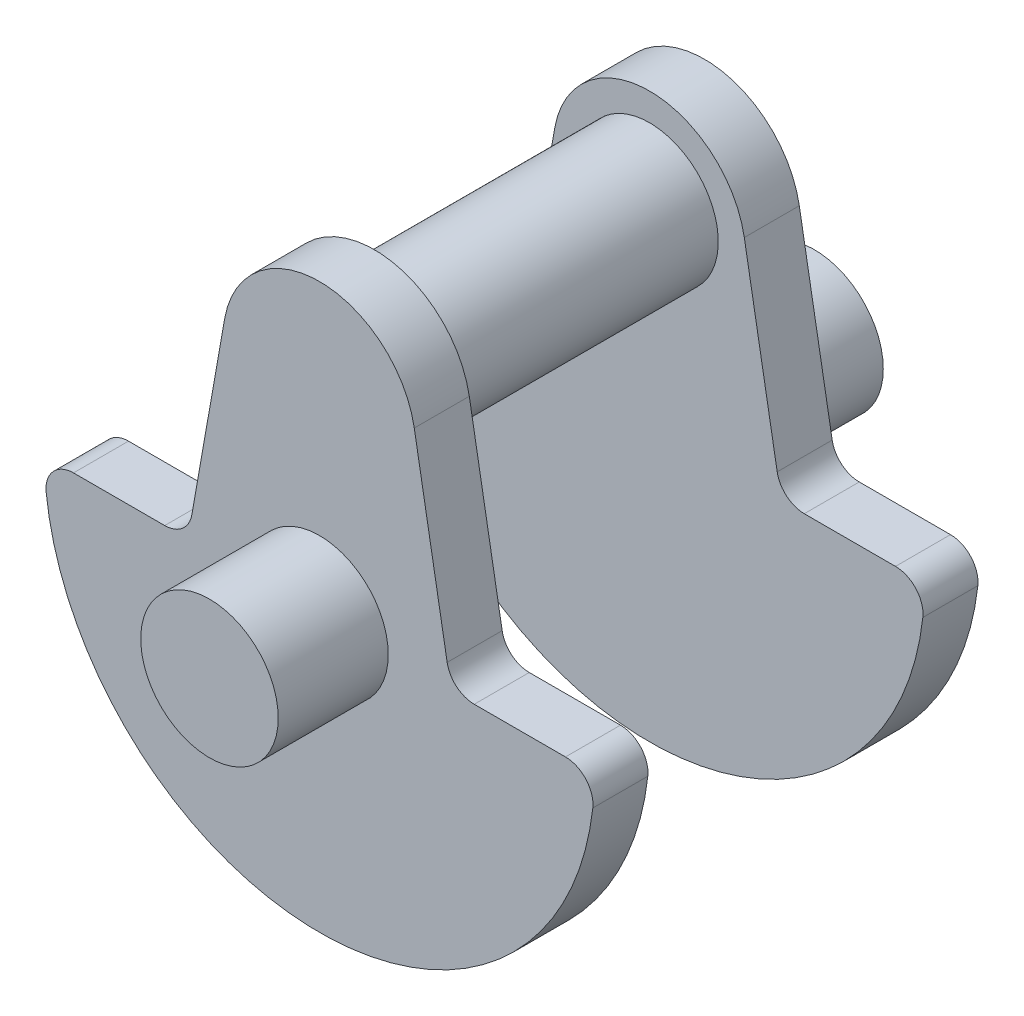
SolidWorks part; units mm, degrees
ref_plane "Front Plane" through (0, 0, 0) normal (0, 0, 1) x (1, 0, 0)
ref_plane "Top Plane" through (0, 0, 0) normal (0, 1, 0) x (1, 0, 0)
ref_plane "Right Plane" through (0, 0, 0) normal (1, 0, 0) x (0, 0, -1)
sketch "Sketch1" plane through (0, 0, 0) normal (0, 0, 1) x (1, 0, 0)
  line L0 (0, -30.5616) -> (0, 74.8057) construction
  line L1 (-56.6461, 0) -> (61.7643, 0) construction
  line L2 (-50, 0) -> (-23.9414, 0)
  line L3 (-23.9414, 0) -> (-17.2341, 38.0388)
  line L4 (23.9414, 0) -> (17.2341, 38.0388)
  line L5 (50, 0) -> (23.9414, 0)
  circle A0 centre (0, 0) radius 12.5
  arc A1 (50, 0) -> (-50, 0) centre (0, 0) cw
  circle A2 centre (0, 35) radius 12.5 construction
  arc A4 (17.2341, 38.0388) -> (-17.2341, 38.0388) centre (0, 35) ccw
  dimension "D1" = 50
  dimension "D3" = 25
  dimension "D4" = 10
  dimension "D5" = 17.5
  dimension "D2" = 35
extrude "Boss-Extrude1" add sketch "Sketch1" along normal blind 10
fillet "Fillet1" radius 5 4 edges at (23.9414, 0, 5) (50, 0, 5) (-50, 0, 5) (-23.9414, 0, 5)
extrude "Boss-Extrude2" add sketch "Sketch1<2>" along normal blind 30 contours A0 region at (0, 0, 0)
sketch "Sketch1<2>" plane through (0, 0, 0) normal (0, 0, 1) x (1, 0, 0) same geometry as "Sketch1"
sketch "Sketch2" plane through (0, 0, 0) normal (0, 0, -1) x (-1, 0, 0)
  circle A0 centre (0, 35) radius 12.5 construction
  circle A1 centre (0, 35) radius 12.5
extrude "Boss-Extrude3" add sketch "Sketch2" along normal blind 50
ref_plane "Plane1" through (0, 0, -25) normal (0, 0, -1) x (-1, 0, 0)
mirror "Mirror1" about plane through (0, 0, -25) normal (0, 0, -1) of "Boss-Extrude2", "Fillet1", "Boss-Extrude1"
